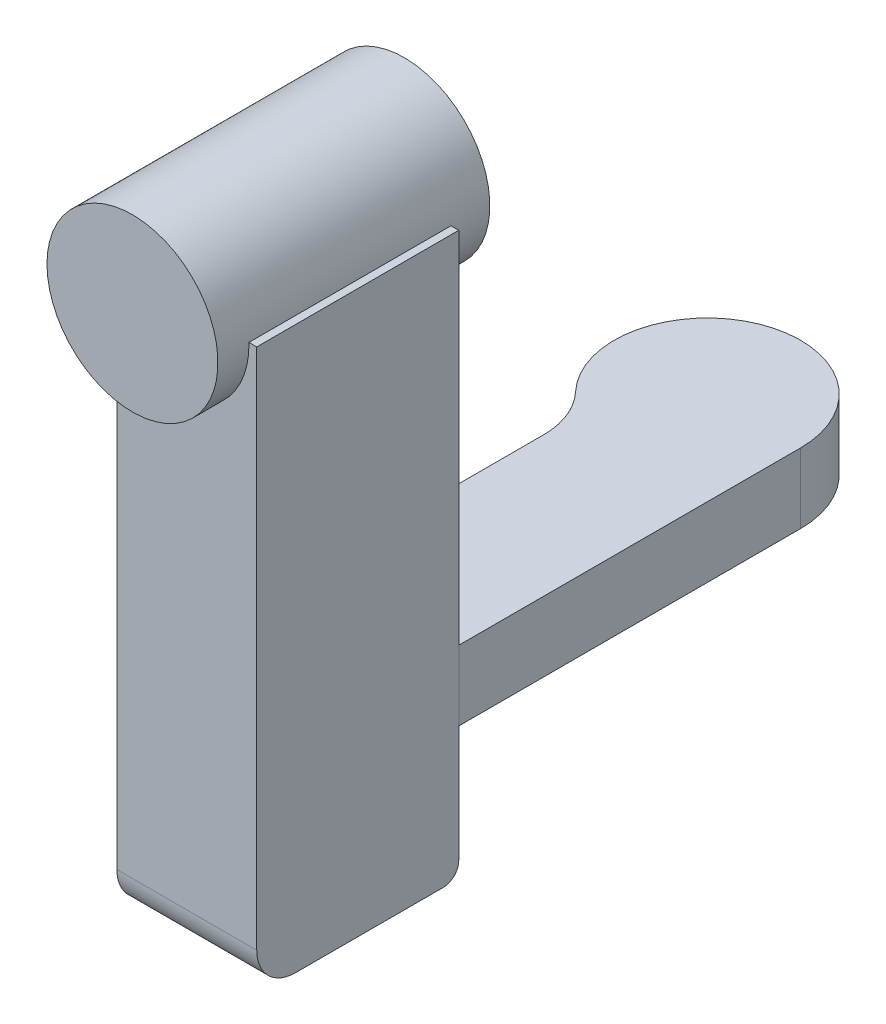
SolidWorks part; units mm, degrees
ref_plane "Front Plane" through (0, 0, 0) normal (0, 0, 1) x (1, 0, 0)
ref_plane "Top Plane" through (0, 0, 0) normal (0, 1, 0) x (1, 0, 0)
ref_plane "Right Plane" through (0, 0, 0) normal (1, 0, 0) x (0, 0, -1)
sketch "Sketch1" plane through (0, 0, 0) normal (0, 1, 0) x (1, 0, 0)
  line L0 (12, 0) -> (12, -44)
  line L1 (12, -44) -> (-6, -44)
  line L2 (-6, -44) -> (-6, -15.0997)
  arc A0 (12, 0) -> (-8.7273, -8.2362) centre (0, 0) ccw
  arc A1 (-6, -15.0997) -> (-8.7273, -8.2362) centre (-16, -15.0997) ccw
  dimension "D1" = 10
extrude "Boss-Extrude1" add sketch "Sketch1" along normal blind 9
ref_plane "Plane2" through (0, 9, 0) normal (0, 1, 0) x (1, 0, 0)
sketch "Sketch2" plane through (0, 9, 0) normal (0, 1, 0) x (1, 0, 0)
  line L1 (12, -44) -> (-6, -44)
  line L2 (12, -44) -> (12, -70)
  line L3 (12, -70) -> (-6, -70)
  line L4 (-6, -44) -> (-6, -70)
  dimension "D1" = 26
extrude "Boss-Extrude2" add sketch "Sketch2" along normal blind 46.257 and the other way blind 26 separate body
fillet "Fillet2" radius 2 1 edges at (3, -17, 44) type face fillet first side face at (3, 19.1285, 44) second side face at (3, -17, 57)
fillet "Fillet3" radius 5 1 edges at (3, -17, 70) type face fillet first side face at (3, -17, 58) second side face at (3, 19.1285, 70)
ref_plane "Plane3" through (0, 0, 44) normal (0, 0, -1) x (-1, 0, 0)
ref_point "Point1"
ref_point "Point2"
ref_axis "Axis1" through (0, -97.3471, 0) along (0, 1, 0)
sketch "Sketch3" plane through (0, 0, 44) normal (0, 0, -1) x (-1, 0, 0)
  line L1 (0, -97.3471) -> (0, 144.7839) construction
  line L2 (13.2, 9) -> (-13.2, 9) construction
  circle A0 centre (0, 55) radius 11
  dimension "D2" = 46
extrude "Boss-Extrude3" add sketch "Sketch3" along normal blind 5 and the other way blind 30
ref_point "Point3"
ref_axis "Axis2" through (0, 55, 74) along (0, 0, -1)
ref_plane "Plane4" through (0, 55, 0) normal (0, 1, 0) x (1, 0, 0)
sketch "Sketch4" plane through (0, 55, 0) normal (0, 1, 0) x (1, 0, 0)
  circle A0 centre (0, 0) radius 15.5211 construction
